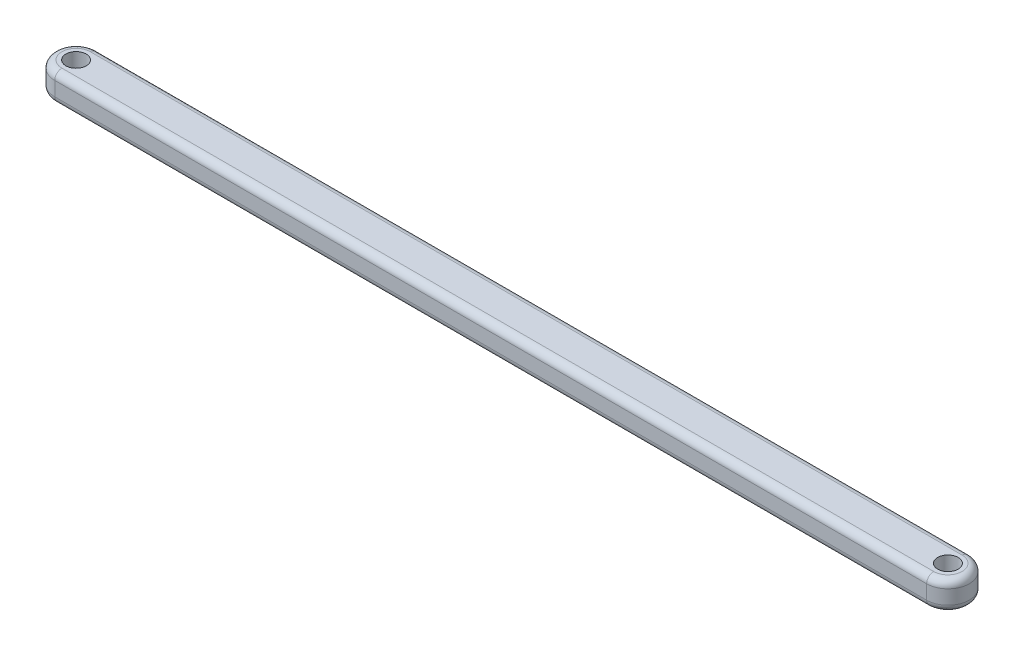
SolidWorks part; units mm, degrees
ref_plane "Front Plane" through (0, 0, 0) normal (0, 0, 1) x (1, 0, 0)
ref_plane "Top Plane" through (0, 0, 0) normal (0, 1, 0) x (1, 0, 0)
ref_plane "Right Plane" through (0, 0, 0) normal (1, 0, 0) x (0, 0, -1)
sketch "Sketch1" plane through (0, 0, 0) normal (0, 1, 0) x (1, 0, 0)
  line L0 (0, 0) -> (194.945, 0) construction
  line L1 (0, 4.7625) -> (194.945, 4.7625)
  line L2 (0, -4.7625) -> (194.945, -4.7625)
  arc A0 (0, 4.7625) -> (0, -4.7625) centre (0, 0) ccw
  arc A1 (194.945, -4.7625) -> (194.945, 4.7625) centre (194.945, 0) ccw
  point P3 (97.4725, 0)
  dimension "D1" = 194.945
  dimension "D2" = 9.525
extrude "Boss-Extrude1" add sketch "Sketch1" along normal mid plane 6.35
sketch "Sketch2" plane through (0, 3.175, 0) normal (0, 1, 0) x (1, 0, 0)
  circle A0 centre (0, 0) radius 2.286
  circle A1 centre (194.945, 0) radius 2.286
  dimension "D1" = 4.572
extrude "Cut-Extrude1" cut sketch "Sketch2" against normal through all
fillet "Fillet1" radius 1.5875 8 edges at (199.7075, -3.175, 0) (97.4725, -3.175, 4.7625) (-4.7625, -3.175, 0) (199.7075, 3.175, 0) (97.4725, 3.175, 4.7625) (-4.7625, 3.175, 0) (97.4725, -3.175, -4.7625) (97.4725, 3.175, -4.7625)
